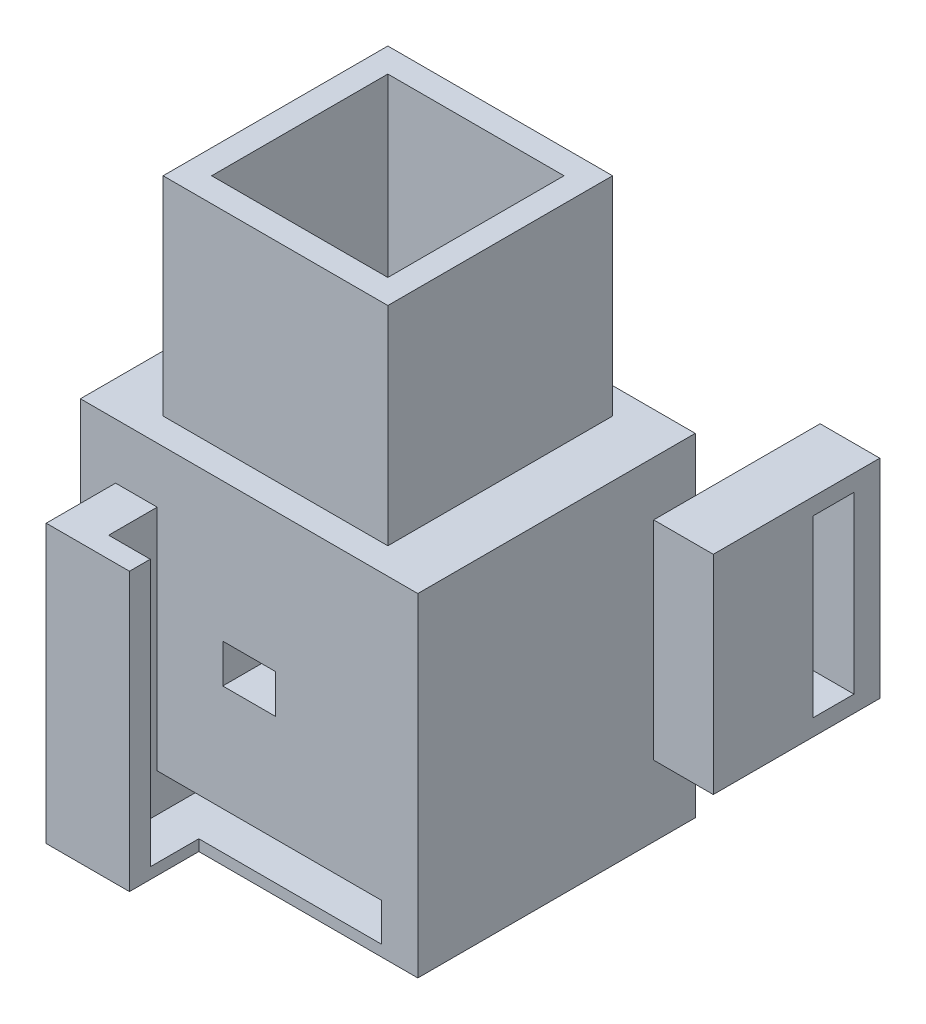
SolidWorks part; units mm, degrees
ref_plane "前基準面" through (0, 0, 0) normal (0, 0, 1) x (1, 0, 0)
ref_plane "上基準面" through (0, 0, 0) normal (0, 1, 0) x (1, 0, 0)
ref_plane "右基準面" through (0, 0, 0) normal (1, 0, 0) x (0, 0, -1)
sketch "草圖1" plane through (0, 0, 0) normal (0, 1, 0) x (1, 0, 0)
  line L1 (-12.16, 10) -> (12.16, 10)
  line L2 (-12.16, 10) -> (-12.16, -10)
  line L3 (-12.16, -10) -> (12.16, -10)
  line L4 (12.16, 10) -> (12.16, -10)
  line L5 (-12.16, 10) -> (12.16, -10) construction
  line L6 (-12.16, -10) -> (12.16, 10) construction
  line L7 (-10.46, 5.08) -> (-7.86, 5.08) construction
  line L8 (-10.46, 5.08) -> (-10.46, -5.08) construction
  line L9 (-10.46, -5.08) -> (-7.86, -5.08) construction
  line L10 (-7.86, 5.08) -> (-7.86, -5.08) construction
  line L11 (-8.1, 8.1) -> (8.1, 8.1)
  line L12 (-8.1, 8.1) -> (-8.1, -8.1)
  line L13 (-8.1, -8.1) -> (8.1, -8.1)
  line L14 (8.1, 8.1) -> (8.1, -8.1)
  line L15 (-8.1, 8.1) -> (8.1, -8.1) construction
  line L16 (-8.1, -8.1) -> (8.1, 8.1) construction
  line L17 (-6.35, 6.35) -> (6.35, 6.35)
  line L18 (-6.35, 6.35) -> (-6.35, -6.35)
  line L19 (-6.35, -6.35) -> (6.35, -6.35)
  line L20 (6.35, 6.35) -> (6.35, -6.35)
  line L21 (-6.35, 6.35) -> (6.35, -6.35) construction
  line L22 (-6.35, -6.35) -> (6.35, 6.35) construction
  point P0 (0, 0)
  point P10 (-9.16, 5.08)
  point P11 (0, 0)
  point P17 (0, 0)
  dimension "D1" = 24.32
  dimension "D2" = 20
  dimension "D3" = 2.6
  dimension "D4" = 10.16
  dimension "D5" = 4.92
  dimension "D6" = 1.7
  dimension "D7" = 16.2
  dimension "D8" = 16.2
  dimension "D9" = 12.7
  dimension "D10" = 12.7
extrude "填料-伸長1" add sketch "草圖1" along normal blind 39 contours L14 L11 L12 L13 L17 L20 L19 L18 region at (0, 0, -7.8709)
sketch "草圖3" plane through (0, 0, 0) normal (0, 1, 0) x (1, 0, 0)
  line L1 (-12.16, 10) -> (12.16, 10)
  line L2 (-12.16, 10) -> (-12.16, -10)
  line L3 (-12.16, -10) -> (12.16, -10)
  line L4 (12.16, 10) -> (12.16, -10)
  line L5 (-12.16, 10) -> (12.16, -10) construction
  line L6 (-12.16, -10) -> (12.16, 10) construction
  line L7 (-10.46, 5.08) -> (-7.86, 5.08) construction
  line L8 (-10.46, 5.08) -> (-10.46, -5.08) construction
  line L9 (-10.46, -5.08) -> (-7.86, -5.08) construction
  line L10 (-7.86, 5.08) -> (-7.86, -5.08) construction
  line L11 (-7.35, 7.35) -> (7.35, 7.35)
  line L12 (-7.35, 7.35) -> (-7.35, -7.35)
  line L13 (-7.35, -7.35) -> (7.35, -7.35)
  line L14 (7.35, 7.35) -> (7.35, -7.35)
  line L15 (-7.35, 7.35) -> (7.35, -7.35) construction
  line L16 (-7.35, -7.35) -> (7.35, 7.35) construction
  line L17 (-6.35, 6.35) -> (6.35, 6.35)
  line L18 (-6.35, 6.35) -> (-6.35, -6.35)
  line L19 (-6.35, -6.35) -> (6.35, -6.35)
  line L20 (6.35, 6.35) -> (6.35, -6.35)
  line L21 (-6.35, 6.35) -> (6.35, -6.35) construction
  line L22 (-6.35, -6.35) -> (6.35, 6.35) construction
  point P0 (0, 0)
  point P10 (-9.16, 5.08)
  point P11 (0, 0)
  point P17 (0, 0)
  dimension "D1" = 24.32
  dimension "D2" = 20
  dimension "D3" = 2.6
  dimension "D4" = 10.16
  dimension "D5" = 4.92
  dimension "D6" = 1.7
  dimension "D7" = 14.7
  dimension "D8" = 14.7
  dimension "D9" = 12.7
  dimension "D10" = 12.7
extrude "填料-伸長2" add sketch "草圖3" along normal blind 4 separate body contours L20 L17 L18 L19 region at (0, 0, 0)
sketch "草圖5" plane through (0, 0, 0) normal (0, 1, 0) x (1, 0, 0)
  line L0 (0, 10) -> (0, -10.2763) construction
  line L1 (-12.16, 10) -> (12.16, 10)
  line L2 (-12.16, 10) -> (-12.16, -10)
  line L3 (-12.16, -10) -> (12.16, -10)
  line L4 (12.16, 10) -> (12.16, -10)
  line L5 (-12.16, 10) -> (12.16, -10) construction
  line L6 (-12.16, -10) -> (12.16, 10) construction
  line L7 (-10.46, 5.08) -> (-7.86, 5.08)
  line L8 (-10.46, 5.08) -> (-10.46, -5.08)
  line L9 (-10.46, -5.08) -> (-7.86, -5.08)
  line L10 (-7.86, 5.08) -> (-7.86, -5.08)
  line L11 (-7.35, 7.35) -> (7.35, 7.35)
  line L12 (-7.35, 7.35) -> (-7.35, -7.35)
  line L13 (-7.35, -7.35) -> (7.35, -7.35)
  line L14 (7.35, 7.35) -> (7.35, -7.35)
  line L15 (-7.35, 7.35) -> (7.35, -7.35) construction
  line L16 (-7.35, -7.35) -> (7.35, 7.35) construction
  line L17 (-6.35, 6.35) -> (6.35, 6.35)
  line L18 (-6.35, 6.35) -> (-6.35, -6.35)
  line L19 (-6.35, -6.35) -> (6.35, -6.35)
  line L20 (6.35, 6.35) -> (6.35, -6.35)
  line L21 (-6.35, 6.35) -> (6.35, -6.35) construction
  line L22 (-6.35, -6.35) -> (6.35, 6.35) construction
  line L23 (10.46, -5.08) -> (7.86, -5.08)
  line L24 (7.86, 5.08) -> (7.86, -5.08)
  line L25 (10.46, 5.08) -> (7.86, 5.08)
  line L26 (10.46, 5.08) -> (10.46, -5.08)
  point P0 (0, 0)
  point P10 (-9.16, 5.08)
  point P11 (0, 0)
  point P17 (0, 0)
  dimension "D1" = 24.32
  dimension "D2" = 20
  dimension "D3" = 2.6
  dimension "D4" = 10.16
  dimension "D5" = 4.92
  dimension "D6" = 1.7
  dimension "D7" = 14.7
  dimension "D8" = 14.7
  dimension "D9" = 12.7
  dimension "D10" = 12.7
extrude "填料-伸長3" add sketch "草圖5" along normal blind 20 contours L4 L1 L2 L3 L7 L10 L9 L8 L11 L14 L13 L12 L25 L26 L23 L24 | L10 L7 L8 L9 | L26 L25 L24 L23 region at (0, 0, -9.6851) region at (-9.16, 0, 0) region at (9.16, 0, 0)
sketch "草圖6" plane through (0, 0, 0) normal (0, 1, 0) x (1, 0, 0)
  line L1 (-12.16, 10) -> (12.16, 10)
  line L2 (-12.16, 10) -> (-12.16, -10)
  line L3 (-12.16, -10) -> (12.16, -10)
  line L4 (12.16, 10) -> (12.16, -10)
  line L5 (-12.16, 10) -> (12.16, -10) construction
  line L6 (-12.16, -10) -> (12.16, 10) construction
  line L7 (-10.46, 5.08) -> (-7.86, 5.08) construction
  line L8 (-10.46, 5.08) -> (-10.46, -5.08) construction
  line L9 (-10.46, -5.08) -> (-7.86, -5.08) construction
  line L10 (-7.86, 5.08) -> (-7.86, -5.08) construction
  line L11 (-7.35, 7.35) -> (7.35, 7.35)
  line L12 (-7.35, 7.35) -> (-7.35, -7.35)
  line L13 (-7.35, -7.35) -> (7.35, -7.35)
  line L14 (7.35, 7.35) -> (7.35, -7.35)
  line L15 (-7.35, 7.35) -> (7.35, -7.35) construction
  line L16 (-7.35, -7.35) -> (7.35, 7.35) construction
  line L17 (-6.35, 6.35) -> (6.35, 6.35)
  line L18 (-6.35, 6.35) -> (-6.35, -6.35)
  line L19 (-6.35, -6.35) -> (6.35, -6.35)
  line L20 (6.35, 6.35) -> (6.35, -6.35)
  line L21 (-6.35, 6.35) -> (6.35, -6.35) construction
  line L22 (-6.35, -6.35) -> (6.35, 6.35) construction
  point P0 (0, 0)
  point P10 (-9.16, 5.08)
  point P11 (0, 0)
  point P17 (0, 0)
  dimension "D1" = 24.32
  dimension "D2" = 20
  dimension "D3" = 2.6
  dimension "D4" = 10.16
  dimension "D5" = 4.92
  dimension "D6" = 1.7
  dimension "D7" = 14.7
  dimension "D8" = 14.7
  dimension "D9" = 12.7
  dimension "D10" = 12.7
sketch "草圖8" plane through (0, 0, 0) normal (0, -1, 0) x (1, 0, 0)
  line L0 (0, 10) -> (0, -10.2763) construction
  line L1 (-12.16, 10) -> (12.16, 10)
  line L2 (-12.16, 10) -> (-12.16, -10)
  line L3 (-12.16, -10) -> (12.16, -10)
  line L4 (12.16, 10) -> (12.16, -10)
  line L5 (-12.16, 10) -> (12.16, -10) construction
  line L6 (-12.16, -10) -> (12.16, 10) construction
  line L7 (-10.46, 5.08) -> (-7.86, 5.08)
  line L8 (-10.46, 5.08) -> (-10.46, -5.08)
  line L9 (-10.46, -5.08) -> (-7.86, -5.08)
  line L10 (-7.86, 5.08) -> (-7.86, -5.08)
  line L11 (-7.35, 7.35) -> (7.35, 7.35)
  line L12 (-7.35, 7.35) -> (-7.35, -7.35)
  line L13 (-7.35, -7.35) -> (7.35, -7.35)
  line L14 (7.35, 7.35) -> (7.35, -7.35)
  line L15 (-7.35, 7.35) -> (7.35, -7.35) construction
  line L16 (-7.35, -7.35) -> (7.35, 7.35) construction
  line L17 (-6.35, 6.35) -> (6.35, 6.35)
  line L18 (-6.35, 6.35) -> (-6.35, -6.35)
  line L19 (-6.35, -6.35) -> (6.35, -6.35)
  line L20 (6.35, 6.35) -> (6.35, -6.35)
  line L21 (-6.35, 6.35) -> (6.35, -6.35) construction
  line L22 (-6.35, -6.35) -> (6.35, 6.35) construction
  line L23 (10.46, -5.08) -> (7.86, -5.08)
  line L24 (7.86, 5.08) -> (7.86, -5.08)
  line L25 (10.46, 5.08) -> (7.86, 5.08)
  line L26 (10.46, 5.08) -> (10.46, -5.08)
  point P0 (0, 0)
  point P10 (-9.16, 5.08)
  point P11 (0, 0)
  point P17 (0, 0)
  dimension "D1" = 24.32
  dimension "D2" = 20
  dimension "D3" = 2.6
  dimension "D4" = 10.16
  dimension "D5" = 4.92
  dimension "D6" = 1.7
  dimension "D7" = 14.7
  dimension "D8" = 14.7
  dimension "D9" = 12.7
  dimension "D10" = 12.7
sketch "草圖9" plane through (0, 0, 0) normal (0, 1, 0) x (1, 0, 0)
  line L0 (0, 10) -> (0, -10.2763) construction
  line L1 (-12.16, 10) -> (12.16, 10)
  line L2 (-12.16, 10) -> (-12.16, -10)
  line L3 (-12.16, -10) -> (12.16, -10)
  line L4 (12.16, 10) -> (12.16, -10)
  line L5 (-12.16, 10) -> (12.16, -10) construction
  line L6 (-12.16, -10) -> (12.16, 10) construction
  line L7 (-10.26, 5.3) -> (-7.52, 5.3)
  line L8 (-10.26, 5.3) -> (-10.26, -5.3)
  line L9 (-10.26, -5.3) -> (-7.52, -5.3)
  line L10 (-7.52, 5.3) -> (-7.52, -5.3)
  line L11 (-7.35, 7.35) -> (7.35, 7.35)
  line L12 (-7.35, 7.35) -> (-7.35, -7.35)
  line L13 (-7.35, -7.35) -> (7.35, -7.35)
  line L14 (7.35, 7.35) -> (7.35, -7.35)
  line L15 (-7.35, 7.35) -> (7.35, -7.35) construction
  line L16 (-7.35, -7.35) -> (7.35, 7.35) construction
  line L17 (-6.35, 6.35) -> (6.35, 6.35)
  line L18 (-6.35, 6.35) -> (-6.35, -6.35)
  line L19 (-6.35, -6.35) -> (6.35, -6.35)
  line L20 (6.35, 6.35) -> (6.35, -6.35)
  line L21 (-6.35, 6.35) -> (6.35, -6.35) construction
  line L22 (-6.35, -6.35) -> (6.35, 6.35) construction
  line L23 (10.26, -5.3) -> (7.52, -5.3)
  line L24 (7.52, 5.3) -> (7.52, -5.3)
  line L25 (10.26, 5.3) -> (7.52, 5.3)
  line L26 (10.26, 5.3) -> (10.26, -5.3)
  line L27 (-8.89, -5.3) -> (-8.89, 5.3) construction
  line L28 (8.89, -5.3) -> (8.89, 4.7757) construction
  line L29 (8.89, 4.7757) -> (8.89, 5.3) construction
  point P0 (0, 0)
  point P10 (-8.89, 5.3)
  point P11 (0, 0)
  point P17 (0, 0)
  dimension "D1" = 24.32
  dimension "D2" = 20
  dimension "D3" = 2.74
  dimension "D4" = 10.6
  dimension "D5" = 4.7
  dimension "D6" = 1.9
  dimension "D7" = 14.7
  dimension "D8" = 14.7
  dimension "D9" = 12.7
  dimension "D10" = 12.7
  dimension "D11" = 17.78
extrude "除料-伸長5" cut sketch "草圖9" along normal blind 8.4167 contours L10 L7 L8 L9 | L26 L25 L24 L23 region at (-8.89, 0, 0) region at (8.89, 0, 0)
sketch "草圖10" plane through (0, 0, 10) normal (0, 0, 1) x (1, 0, 0)
  line L1 (-2.63, 18) -> (2.63, 18)
  line L2 (-2.63, 18) -> (-2.63, 13.6)
  line L3 (-2.63, 13.6) -> (2.63, 13.6)
  line L4 (2.63, 18) -> (2.63, 13.6)
  line L5 (-12.16, 20) -> (-12.16, 0) construction
  line L6 (-12.16, 0) -> (12.16, 0) construction
  dimension "D1" = 5.26
  dimension "D2" = 4.4
  dimension "D3" = 9.53
  dimension "D4" = 13.6
extrude "除料-伸長6" [suppressed] cut sketch "草圖10" against normal up to next
sketch "草圖12" plane through (0, 0, 10) normal (0, 0, 1) x (1, 0, 0)
  line L0 (-12.16, 10) -> (12.16, 10) construction
  line L1 (-12.16, 20) -> (-12.16, 0) construction
  line L2 (12.16, 20) -> (12.16, 0) construction
  line L3 (-12.16, 0) -> (12.16, 0) construction
  dimension "D1" = 10
ref_plane "平面1" through (0, 10, 0) normal (0, 1, 0) x (1, 0, 0)
sketch "草圖11" plane through (0, 10, 0) normal (0, 1, 0) x (1, 0, 0)
  line L0 (-12.16, -10) -> (12.16, -10) construction
  line L1 (-3, -10) -> (3, -10)
  line L2 (-3, -10) -> (-3, -13)
  line L3 (-3, -13) -> (3, -13)
  line L4 (3, -10) -> (3, -13)
  line L5 (0, -10) -> (0, -13) construction
  line L6 (12.16, 10) -> (12.16, -10) construction
  line L7 (-12.16, 10) -> (-12.16, -10) construction
  circle A0 centre (-1.7, -11.5) radius 0.4
  circle A1 centre (1.7, -11.5) radius 0.4
  dimension "D3" = 0.8
  dimension "D7" = 3.4
  dimension "D1" = 6
  dimension "D2" = 3
  dimension "D5" = 1.5
  dimension "D6" = 1.5
  dimension "D8" = 1.3
extrude "填料-伸長5" [suppressed] add sketch "草圖11" along normal blind 1.5
sketch "草圖13" plane through (0, 0, -10) normal (0, 0, -1) x (-1, 0, 0)
  line L0 (0, 15.4) -> (0, 9.8) construction
  line L1 (-2.8, 15.4) -> (2.8, 15.4)
  line L2 (-2.8, 15.4) -> (-2.8, 9.8)
  line L3 (-2.8, 9.8) -> (2.8, 9.8)
  line L4 (2.8, 15.4) -> (2.8, 9.8)
  line L5 (12.16, 20) -> (12.16, 0) construction
  line L6 (-12.16, 20) -> (-12.16, 0) construction
  line L7 (-4.2, 16.8) -> (-4.2, 8.4)
  line L8 (-4.2, 8.4) -> (4.2, 8.4)
  line L9 (4.2, 16.8) -> (4.2, 8.4)
  line L10 (-4.2, 16.8) -> (4.2, 16.8)
  line L11 (12.16, 20) -> (-12.16, 20) construction
  dimension "D1" = 5.6
  dimension "D2" = 5.6
  dimension "D4" = 4.6
  dimension "D3" = 1.4
extrude "填料-伸長6" add sketch "草圖13" along normal blind 5.1
sketch "草圖15" plane through (0, 0, -10) normal (0, 0, -1) x (-1, 0, 0)
  line L1 (-2.8, 15.4) -> (2.8, 15.4) construction
  line L2 (-2.8, 15.4) -> (-2.8, 9.8) construction
  line L3 (-2.8, 9.8) -> (2.8, 9.8) construction
  line L4 (2.8, 15.4) -> (2.8, 9.8) construction
  circle A0 centre (0, 15.8) radius 2.65
  dimension "D1" = 5.3
extrude "除料-伸長7" [suppressed] cut sketch "草圖15" against normal up to next
sketch "草圖16" plane through (0, 0, -10) normal (0, 0, -1) x (-1, 0, 0)
  line L0 (12.16, 0) -> (-12.16, 0) construction
  line L1 (-4.2, 10.6) -> (4.2, 10.6)
  line L2 (-4.2, 10.6) -> (-4.2, 9)
  line L3 (-4.2, 9) -> (4.2, 9)
  line L4 (4.2, 10.6) -> (4.2, 9)
  line L5 (0, 10.6) -> (0, 9) construction
  line L7 (12.16, 20) -> (12.16, 0) construction
  line L8 (-12.16, 20) -> (-12.16, 0) construction
  dimension "D1" = 8.4
  dimension "D2" = 1.6
  dimension "D3" = 9
extrude "填料-伸長7" [suppressed] add sketch "草圖16" along normal blind 7.4
sketch "草圖17" [suppressed] plane through (0, 10.6, 0) normal (0, 1, 0) x (1, 0, 0)
  line L0 (-4.2, 17.4) -> (4.2, 17.4) construction
  line L1 (4.2, 17.4) -> (4.2, 10) construction
  circle A0 centre (1.27, 16.15) radius 0.4
  circle A1 centre (-1.27, 16.15) radius 0.4
  dimension "D1" = 0.8
  dimension "D2" = 0.8
  dimension "D3" = 1.25
  dimension "D4" = 1.25
  dimension "D5" = 2.54
  dimension "D6" = 2.93
extrude "除料-伸長8" [suppressed] cut sketch "草圖17" against normal up to next
sketch "草圖18" plane through (0, 39, 0) normal (0, 1, 0) x (1, 0, 0)
sketch "草圖20" [suppressed] plane through (0, 0, -10) normal (0, 0, -1) x (-1, 0, 0)
  line L1 (-2.8, 18.6) -> (2.8, 18.6)
  line L2 (-2.8, 18.6) -> (-2.8, 13)
  line L3 (-2.8, 13) -> (2.8, 13)
  line L4 (2.8, 18.6) -> (2.8, 13)
  line L5 (-2.8, 18.6) -> (2.8, 13) construction
  line L6 (-2.8, 13) -> (2.8, 18.6) construction
  circle A0 centre (0, 15.8) radius 2.65
  dimension "D1" = 5.3
  dimension "D2" = 5.6
  dimension "D3" = 5.6
extrude "填料-伸長8" [suppressed] add sketch "草圖20" along normal blind 3.7
sketch "草圖21" [suppressed] plane through (0, 0, -10) normal (0, 0, -1) x (-1, 0, 0)
  line L0 (-4.2, 11.6) -> (4.2, 11.6) construction
  line L1 (-4.2, 10.6) -> (4.2, 10.6)
  line L2 (-4.2, 10.6) -> (-4.2, 11.6)
  line L3 (-4.2, 11.6) -> (4.2, 11.6)
  line L4 (4.2, 10.6) -> (4.2, 11.6)
  dimension "D1" = 8.4
extrude "填料-伸長9" [suppressed] add sketch "草圖21" along normal blind 5.1
sketch "草圖23" plane through (0, 0, 10) normal (0, 0, 1) x (1, 0, 0)
  line L0 (7.3, 20) -> (-7.3, 20)
  line L1 (-7.3, 20) -> (-7.3, 0.8)
  line L2 (-7.3, 0.8) -> (7.3, 0.8)
  line L3 (7.3, 0.8) -> (7.3, 20)
  line L4 (1.9, 14) -> (-1.9, 14)
  line L5 (-1.9, 14) -> (-1.9, 11.2)
  line L6 (-1.9, 11.2) -> (1.9, 11.2)
  line L7 (1.9, 11.2) -> (1.9, 14)
  line L8 (12.16, 20) -> (12.16, 0) construction
  line L9 (-12.16, 0) -> (12.16, 0) construction
  line L12 (6.625, 0.8) -> (-6.625, 0.8)
  line L15 (-6.625, 3.54) -> (6.625, 3.54)
  line L16 (-6.625, 3.54) -> (-6.625, 0.8)
  line L17 (-6.625, 0.8) -> (6.625, 0.8)
  line L18 (6.625, 3.54) -> (6.625, 0.8)
  point P18 (0, 3.54)
  dimension "D2" = 14.6
  dimension "D3" = 2.8
  dimension "D4" = 3.8
  dimension "D5" = 5.4
  dimension "D6" = 10.4
  dimension "D7" = 4.86
  dimension "D8" = 19.2
  dimension "D9" = 13.25
  dimension "D10" = 2.74
  dimension "D11" = 7.3
  dimension "D12" = 0.8
sketch "草圖26" plane through (0, 0, -10) normal (0, 0, -1) x (-1, 0, 0)
  line L0 (4.5, 20.1) -> (4.5, 5.1) construction
  line L1 (4.5, 5.1) -> (-12, 5.1) construction
  line L2 (-12, 5.1) -> (-12, 20.1) construction
  line L3 (-12, 20.1) -> (4.5, 20.1) construction
  line L4 (12.16, 20) -> (12.16, 0) construction
  line L5 (12.16, 0) -> (-12.16, 0) construction
  dimension "D1" = 15
  dimension "D2" = 16.5
  dimension "D3" = 7.66
  dimension "D4" = 5.1
sketch "草圖27" plane through (0, 0, -10) normal (0, 0, -1) x (-1, 0, 0)
  line L1 (2.8, 15.4) -> (-2.8, 9.8) construction
  line L2 (-2.8, 15.4) -> (2.8, 9.8) construction
  line L3 (-2.8, 15.4) -> (2.8, 15.4)
  line L4 (-2.8, 15.4) -> (-2.8, 9.8)
  line L5 (-2.8, 9.8) -> (2.8, 9.8)
  line L6 (2.8, 15.4) -> (2.8, 9.8)
  circle A0 centre (0, 12.6) radius 2.65
  dimension "D1" = 5.3
extrude "填料-伸長10" add sketch "草圖27" along normal blind 3.7
sketch "草圖33" plane through (0, 0, -10) normal (0, 0, -1) x (-1, 0, 0)
  circle A2 centre (0, 12.6) radius 2.65
  dimension "D1" = 5.3
extrude "除料-伸長10" cut sketch "草圖33" against normal up to next
extrude "除料-伸長13" cut sketch "草圖23" against normal up to next contours L6 L7 L4 L5 region at (0, 12.6, 10)
sketch "草圖34" plane through (0, 20, 0) normal (0, 1, 0) x (1, 0, 0)
  line L1 (-12.16, -10) -> (12.16, -10)
  line L2 (-12.16, -10) -> (-12.16, 10)
  line L3 (-12.16, 10) -> (12.16, 10)
  line L4 (12.16, -10) -> (12.16, 10)
  line L5 (-8.1, 8.1) -> (8.1, 8.1)
  line L6 (-8.1, 8.1) -> (-8.1, -8.1)
  line L7 (-8.1, -8.1) -> (8.1, -8.1)
  line L8 (8.1, 8.1) -> (8.1, -8.1)
extrude "填料-伸長11" add sketch "草圖34" along normal blind 4
sketch "草圖35" plane through (12.16, 0, 0) normal (1, 0, 0) x (0, 0, -1)
  line L0 (10, 0) -> (-10, 0) construction
  line L1 (7, 20.1) -> (10, 20.1)
  line L2 (7, 20.1) -> (7, 5.1)
  line L3 (7, 5.1) -> (10, 5.1)
  line L4 (10, 20.1) -> (10, 5.1)
  line L5 (-10, 24) -> (-10, 0) construction
  dimension "D1" = 15
  dimension "D2" = 3
  dimension "D3" = 5.1
  dimension "D4" = 17
extrude "填料-伸長12" add sketch "草圖35" along normal blind 4.3
sketch "草圖38" plane through (0, 0, -10) normal (0, 0, -1) x (-1, 0, 0)
  line L1 (-12.16, 20.1) -> (-16.46, 20.1)
  line L2 (-12.16, 20.1) -> (-12.16, 5.1)
  line L3 (-12.16, 5.1) -> (-16.46, 5.1)
  line L4 (-16.46, 20.1) -> (-16.46, 5.1)
  line L5 (12.16, 0) -> (-12.16, 0) construction
  line L6 (-16.46, 5.1) -> (-16.46, 20.1) construction
  dimension "D1" = 15
  dimension "D2" = 4.3
  dimension "D3" = 5.1
  dimension "D4" = 0
extrude "填料-伸長13" add sketch "草圖38" along normal blind 9
sketch "草圖39" plane through (16.46, 0, 0) normal (1, 0, 0) x (0, 0, -1)
  line L0 (10, 5.1) -> (10, 20.1) construction
  line L1 (14.2, 18.9) -> (17.14, 18.9)
  line L2 (14.2, 18.9) -> (14.2, 6.3)
  line L3 (14.2, 6.3) -> (17.14, 6.3)
  line L4 (17.14, 18.9) -> (17.14, 6.3)
  line L5 (19, 5.1) -> (7, 5.1) construction
  dimension "D1" = 12.6
  dimension "D2" = 2.94
  dimension "D3" = 4.2
  dimension "D4" = 1.2
extrude "除料-伸長14" cut sketch "草圖39" against normal up to next
extrude "除料-伸長16" cut sketch "草圖23<4>" against normal blind 10 contours L18 L15 L16 L2 region at (0, 2.17, 10)
sketch "草圖23<4>" plane through (0, 0, 10) normal (0, 0, 1) x (1, 0, 0) same geometry as "草圖23"
sketch "草圖42" plane through (0, 0, 10) normal (0, 0, 1) x (1, 0, 0)
  line L0 (-12.16, 0) -> (12.16, 0) construction
  line L1 (-6.625, 20) -> (-9.625, 20)
  line L2 (-6.625, 20) -> (-6.625, 0.8)
  line L3 (-6.625, 0.8) -> (-9.625, 0.8)
  line L4 (-9.625, 20) -> (-9.625, 0.8)
  line L8 (-12.16, 24) -> (-12.16, 0) construction
  dimension "D1" = 19.2
  dimension "D2" = 0.8
  dimension "D3" = 3
  dimension "D4" = 2.535
extrude "填料-伸長14" add sketch "草圖42" along normal blind 5
sketch "草圖45" plane through (-6.625, 0, 0) normal (1, 0, 0) x (0, 0, -1)
  line L0 (-15, 0.8) -> (-10, 0.8) construction
  line L1 (-15, 20) -> (-13.5, 20)
  line L2 (-15, 20) -> (-15, 0.8)
  line L3 (-15, 0.8) -> (-13.5, 0.8)
  line L4 (-13.5, 20) -> (-13.5, 0.8)
  dimension "D1" = 1.5
extrude "填料-伸長15" add sketch "草圖45" along normal blind 3
sketch "草圖46" plane through (0, 0, 10) normal (0, 0, 1) x (1, 0, 0)
  line L1 (6.625, 3.54) -> (9.56, 3.54)
  line L2 (6.625, 3.54) -> (6.625, 0.8)
  line L3 (6.625, 0.8) -> (9.56, 0.8)
  line L4 (9.56, 3.54) -> (9.56, 0.8)
  line L5 (16.46, 20.1) -> (16.46, 5.1) construction
  dimension "D1" = 6.9
  dimension "D2" = 2.74
extrude "除料-伸長18" cut sketch "草圖46" against normal blind 10 contours L2 L1 L4 L3
sketch "草圖47" plane through (0, 0, 0) normal (0, 0, 1) x (1, 0, 0)
  line L0 (-6.625, 0.8) -> (7.52, 0.8) construction
  line L1 (-6.625, 3.54) -> (3.975, 3.54)
  line L2 (-6.625, 3.54) -> (-6.625, 0.8)
  line L3 (-6.625, 0.8) -> (3.975, 0.8)
  line L4 (3.975, 3.54) -> (3.975, 0.8)
  dimension "D1" = 10.6
extrude "除料-伸長19" cut sketch "草圖47" against normal up to next
sketch "草圖49" plane through (0, 0, 10) normal (0, 0, 1) x (1, 0, 0)
  line L0 (-12.16, 0) -> (12.16, 0) construction
  line L1 (-9.625, 0.8) -> (-3.625, 0.8)
  line L2 (-9.625, 0.8) -> (-9.625, 0)
  line L3 (-9.625, 0) -> (-3.625, 0)
  line L4 (-3.625, 0.8) -> (-3.625, 0)
  dimension "D1" = 6
extrude "填料-伸長17" add sketch "草圖49" along normal blind 5 contours L2 L1 L4 L3
